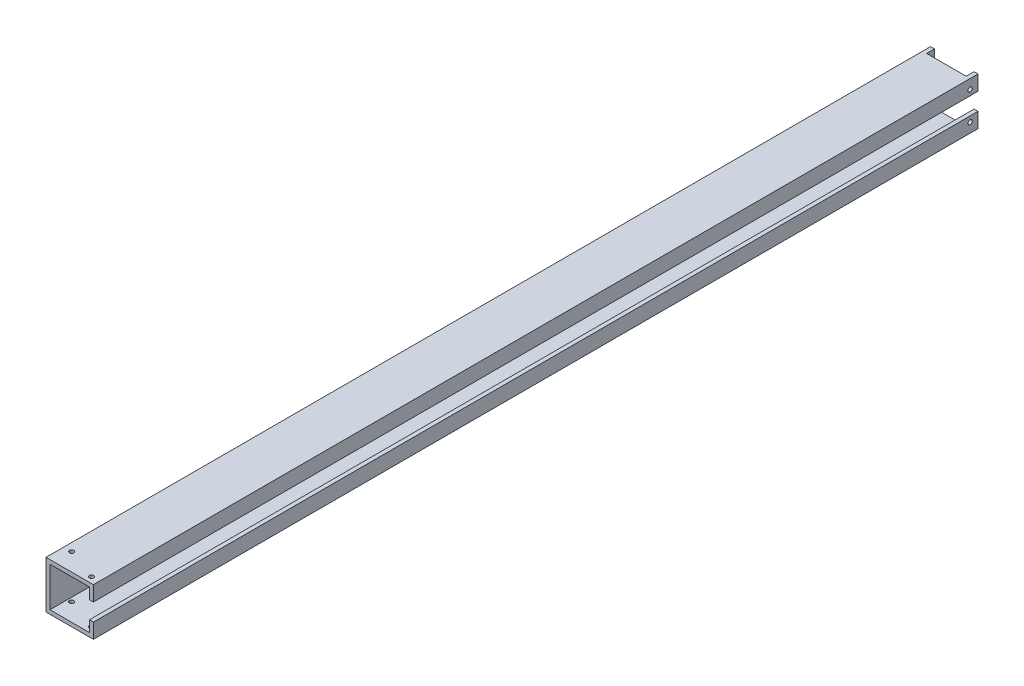
SolidWorks part; units mm, degrees
ref_plane "Front Plane" through (0, 0, 0) normal (1, 0, 0) x (0, 1, 0)
ref_plane "Top Plane" through (0, 0, 0) normal (0, 0, 1) x (0, 1, 0)
ref_plane "Right Plane" through (0, 0, 0) normal (0, 1, 0) x (-1, 0, 0)
sketch "Sketch1" plane through (0, 0, 0) normal (0, 0, 1) x (0, 1, 0)
  line L0 (19.05, -19.05) -> (19.05, 19.05)
  line L1 (19.05, -19.05) -> (-19.05, -19.05)
  line L2 (19.05, -19.05) -> (19.05, 19.05)
  line L3 (19.05, 19.05) -> (-19.05, 19.05)
  line L4 (-19.05, -19.05) -> (-19.05, 19.05)
  line L5 (19.05, -19.05) -> (-19.05, 19.05) construction
  line L6 (19.05, 19.05) -> (-19.05, -19.05) construction
  line L7 (19.05, 19.05) -> (-19.05, 19.05)
  line L8 (-19.05, -19.05) -> (-19.05, 19.05)
  line L9 (19.05, -19.05) -> (-19.05, -19.05)
  line L10 (15.875, 15.875) -> (-15.875, 15.875)
  line L11 (-15.875, -15.875) -> (-15.875, 15.875)
  line L12 (15.875, -15.875) -> (-15.875, -15.875)
  line L13 (15.875, -15.875) -> (15.875, 15.875)
  line L14 (-6.985, -15.875) -> (-6.985, -19.05)
  line L15 (6.985, -15.875) -> (6.985, -19.05)
  line L16 (-15.875, -15.875) -> (-6.985, -15.875)
  line L17 (-6.985, -17.4625) -> (-19.05, -17.4625) construction
  line L18 (6.985, -17.4625) -> (19.05, -17.4625) construction
  point P0 (0, 0)
  dimension "D1" = 38.1
  dimension "D4" = 13.97
  dimension "D2" = 0
  dimension "D3" = 3.175
extrude "Boss-Extrude1" add sketch "Sketch1" along normal blind 711.2 contours L4 L1 L0 L3 L13 L12 L11 L10 region at (18.5112, 13.0175, 0)
sketch "Sketch6" plane through (0, 0, 0) normal (0, 0, 1) x (0, 1, 0)
  line L1 (26.9875, -26.9875) -> (-26.9875, -26.9875) construction
  line L2 (26.9875, -26.9875) -> (26.9875, 26.9875) construction
  line L3 (26.9875, 26.9875) -> (-26.9875, 26.9875) construction
  line L4 (-26.9875, -26.9875) -> (-26.9875, 26.9875) construction
  line L5 (26.9875, -26.9875) -> (-26.9875, 26.9875) construction
  line L6 (26.9875, 26.9875) -> (-26.9875, -26.9875) construction
  line L11 (-26.9875, 25.8156) -> (-16.9875, 25.8156)
  line L12 (-26.9875, 25.8156) -> (-26.9875, 21.8156)
  line L13 (-26.9875, 21.8156) -> (-16.9875, 21.8156)
  line L14 (-16.9875, 25.8156) -> (-16.9875, 21.8156)
  line L15 (-23.4875, 25.8156) -> (-20.4875, 25.8156)
  line L16 (-23.4875, 25.8156) -> (-23.4875, -2.5726)
  line L17 (-23.4875, -2.5726) -> (-20.4875, -2.5726)
  line L18 (-20.4875, 25.8156) -> (-20.4875, -2.5726)
  point P0 (0, 0)
  point P14 (-21.9875, 25.8156)
  point P15 (-21.9875, 25.8156)
  dimension "D1" = 53.975
  dimension "D2" = 4
  dimension "D3" = 10
  dimension "D4" = 3
sketch "Sketch7" plane through (0, 0, 0) normal (0, 1, 0) x (-1, 0, 0)
  line L0 (-19.05, 711.2) -> (19.05, 711.2) construction
  line L1 (-12.7, 708.1875) -> (-12.7, 704.6875) construction
  line L2 (12.7, 696.9125) -> (-12.7, 696.9125) construction
  line L3 (12.7, 696.9125) -> (12.7, 706.4375) construction
  line L4 (12.7, 706.4375) -> (-12.7, 706.4375) construction
  line L5 (-12.7, 696.9125) -> (-12.7, 706.4375) construction
  line L6 (12.7, 696.9125) -> (-12.7, 706.4375) construction
  line L7 (12.7, 706.4375) -> (-12.7, 696.9125) construction
  line L8 (-19.05, 711.2) -> (-19.05, 0) construction
  circle A0 centre (-12.7, 706.4375) radius 1.75
  circle A1 centre (12.7, 696.9125) radius 1.75
  point P0 (0, 711.2)
  point P2 (0, 701.675)
  dimension "D2" = 3.5
  dimension "D1" = 9.525
  dimension "D3" = 4.7625
  dimension "D4" = 6.35
extrude "Cut-Extrude2" cut sketch "Sketch7" along normal blind 70.104 and the other way blind 58.42
sketch "Sketch8" plane through (0, 19.05, 0) normal (0, 1, 0) x (-1, 0, 0)
  line L0 (-19.05, 0) -> (19.05, 0) construction
  line L1 (15.875, -6.35) -> (-15.875, -6.35)
  line L2 (15.875, -6.35) -> (15.875, 6.35)
  line L3 (15.875, 6.35) -> (-15.875, 6.35)
  line L4 (-15.875, -6.35) -> (-15.875, 6.35)
  line L5 (15.875, -6.35) -> (-15.875, 6.35) construction
  line L6 (15.875, 6.35) -> (-15.875, -6.35) construction
  point P0 (0, 0)
  dimension "1.25" = 31.75
  dimension "D2" = 6.35
extrude "Cut-Extrude3" cut sketch "Sketch8" against normal blind 71.882
sketch "Sketch9" plane through (19.05, 0, 0) normal (1, 0, 0) x (0, 1, 0)
  line L0 (19.05, 0) -> (6.985, 0) construction
  line L1 (-6.985, 0) -> (-19.05, 0) construction
  line L2 (19.05, 0) -> (6.985, 0) construction
  line L3 (-6.985, 0) -> (-19.05, 0) construction
  line L4 (15.875, 6.35) -> (19.05, 6.35) construction
  line L5 (-19.05, 6.35) -> (-15.875, 6.35) construction
  line L6 (15.875, 6.35) -> (19.05, 6.35) construction
  line L7 (-19.05, 6.35) -> (-15.875, 6.35) construction
  line L8 (-15.875, 6.35) -> (-6.985, 6.35) construction
  line L9 (-6.985, 711.2) -> (-6.985, 0) construction
  line L10 (0, 0) -> (0, 6.35) construction
  circle A0 centre (-11.43, 6.35) radius 1.75
  circle A2 centre (11.43, 6.35) radius 1.75
  point P15 (-11.43, 6.35)
  dimension "D2" = 3.5
  dimension "D1" = 0
extrude "Cut-Extrude4" cut sketch "Sketch9" against normal blind 68.326
